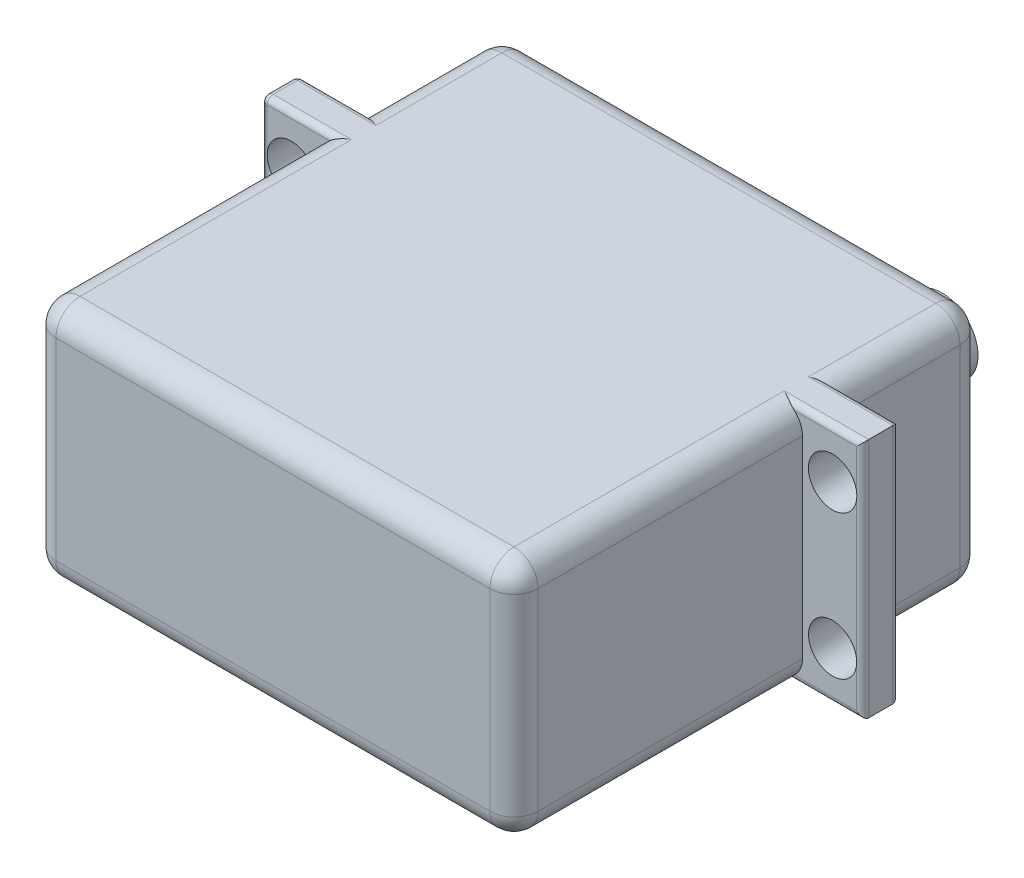
SolidWorks part; units mm, degrees
ref_plane "前视基准面" through (0, 0, 0) normal (0, 0, 1) x (1, 0, 0)
ref_plane "上视基准面" through (0, 0, 0) normal (0, 1, 0) x (1, 0, 0)
ref_plane "右视基准面" through (0, 0, 0) normal (1, 0, 0) x (0, 0, -1)
other "Configuration Table"
sketch "草图3" plane through (0, 0, 0) normal (0, 0, 1) x (1, 0, 0)
  line L1 (-73.7936, 13.2536) -> (-33.7936, 13.2536)
  line L2 (-73.7936, 13.2536) -> (-73.7936, -6.7464)
  line L3 (-73.7936, -6.7464) -> (-33.7936, -6.7464)
  line L4 (-33.7936, 13.2536) -> (-33.7936, -6.7464)
extrude "凸台-拉伸2" add sketch "草图3" along normal blind 39
sketch "草图4" plane through (-33.7936, 0, 0) normal (1, 0, 0) x (0, 0, -1)
  line L0 (-39, 13.2536) -> (0, 13.2536) construction
  line L1 (-15.0684, 13.2536) -> (-12.0684, 13.2536)
  line L2 (-15.0684, 13.2536) -> (-15.0684, -6.7464)
  line L3 (-15.0684, -6.7464) -> (-12.0684, -6.7464)
  line L4 (-12.0684, 13.2536) -> (-12.0684, -6.7464)
  line L5 (-39, -6.7464) -> (0, -6.7464) construction
extrude "凸台-拉伸3" add sketch "草图4" along normal blind 5
sketch "草图7" plane through (-73.7936, 0, 0) normal (-1, 0, 0) x (0, 0, 1)
  line L0 (39, 13.2536) -> (0, 13.2536) construction
  line L1 (11.9737, 13.2536) -> (14.9737, 13.2536)
  line L2 (11.9737, 13.2536) -> (11.9737, -6.7464)
  line L3 (11.9737, -6.7464) -> (14.9737, -6.7464)
  line L4 (14.9737, 13.2536) -> (14.9737, -6.7464)
  line L5 (39, -6.7464) -> (0, -6.7464) construction
sketch "草图8" plane through (-73.7936, 0, 0) normal (-1, 0, 0) x (0, 0, 1)
extrude "凸台-拉伸4" add sketch "草图7" along normal blind 5 contours L2 L1 L4 L3
sketch "草图9" plane through (0, 0, 11.9737) normal (0, 0, -1) x (-1, 0, 0)
  circle A0 centre (76.2936, 9.1421) radius 2
  circle A1 centre (76.2936, -3) radius 2
extrude "切除-拉伸1" cut sketch "草图9" against normal blind 3 contours A0 | A1
sketch "草图10" plane through (0, 0, 12.0684) normal (0, 0, -1) x (-1, 0, 0)
  circle A1 centre (31.2936, 9.199) radius 2.0091
  circle A3 centre (31.2936, -2.7464) radius 2
extrude "切除-拉伸2" cut sketch "草图10" against normal blind 3 contours A1 | A3
sketch "草图11" plane through (0, 0, 0) normal (0, 0, -1) x (-1, 0, 0)
  circle A0 centre (43.2939, 3.2536) radius 7
  circle A1 centre (43.2939, 3.2536) radius 5.6
  circle A2 centre (43.2939, 3.2536) radius 3
extrude "凸台-拉伸6" add sketch "草图11" along normal blind 6 contours A2
sketch "草图14" plane through (0, 0, 0) normal (0, 0, -1) x (-1, 0, 0)
sketch "草图15" plane through (-73.7936, 0, 0) normal (-1, 0, 0) x (0, 0, 1)
sketch "草图16" plane through (0, 0, 0) normal (0, 0, -1) x (-1, 0, 0)
  circle A0 centre (43.2939, 3.2536) radius 6
extrude "凸台-拉伸8" add sketch "草图16" along normal blind 1.5
sketch "草图17" plane through (0, 0, 0) normal (0, 0, -1) x (-1, 0, 0)
  circle A0 centre (43.2939, 3.2536) radius 7
extrude "凸台-拉伸9" add sketch "草图17" along normal blind 1 contours A0
hole_wizard "#3-48 螺纹孔的螺纹孔钻头1" positions "草图32" profile "草图33" hole size "#3-48" standard "ANSI Inch"
sketch "草图32" plane through (0, 0, -6) normal (0, 0, -1) x (-1, 0, 0)
  point P0 (43.2939, 3.2536)
sketch "草图33" plane through (-43.2939, 3.2536, -6) normal (1, 0, 0) x (0, 1, 0)
  line L0 (0, 0) -> (0, 3.599)
  line L1 (0, 3.599) -> (0.9969, 3)
  line L2 (0.9969, 3) -> (0.9969, 0)
  line L5 (0.9969, 0) -> (0, 0)
  line L10 (0, 3.599) -> (-0.997, 3) construction
  line L11 (0, -6.35) -> (0, 107.95) construction
  dimension "孔直径" = 1.9939
  dimension "孔深度" = 3
  dimension "导头角度" = 118
fillet "圆角2" radius 2 8 edges at (-33.7936, 13.2536, 6.0342) (-53.7936, 13.2536, 0) (-73.7936, 13.2536, 5.9868) (-73.7936, -6.7464, 5.9868) (-73.7936, 3.2536, 0) (-53.7936, -6.7464, 0) (-33.7936, 3.2536, 0) (-33.7936, -6.7464, 6.0342)
fillet "圆角5" radius 2 8 edges at (-73.7936, 13.2536, 26.9868) (-73.7936, -6.7464, 26.9868) (-73.7936, 3.2536, 39) (-53.7936, -6.7464, 39) (-33.7936, -6.7464, 27.0342) (-33.7936, 3.2536, 39) (-53.7936, 13.2536, 39) (-33.7936, 13.2536, 27.0342)
fillet "圆角6" radius 0.5 6 edges at (-32.2936, 13.2536, 15.0684) (-32.2936, 13.2536, 12.0684) (-32.2936, -6.7464, 15.0684) (-28.7936, 3.2536, 15.0684) (-28.7936, 3.2536, 12.0684) (-32.2936, -6.7464, 12.0684)
fillet "圆角7" radius 0.5 8 edges at (-75.2936, -6.7464, 14.9737) (-75.2936, -6.7464, 11.9737) (-78.7936, -6.7464, 13.4737) (-78.7936, 3.2536, 14.9737) (-75.2936, 13.2536, 14.9737) (-78.7936, 13.2536, 13.4737) (-78.7936, 3.2536, 11.9737) (-75.2936, 13.2536, 11.9737)
